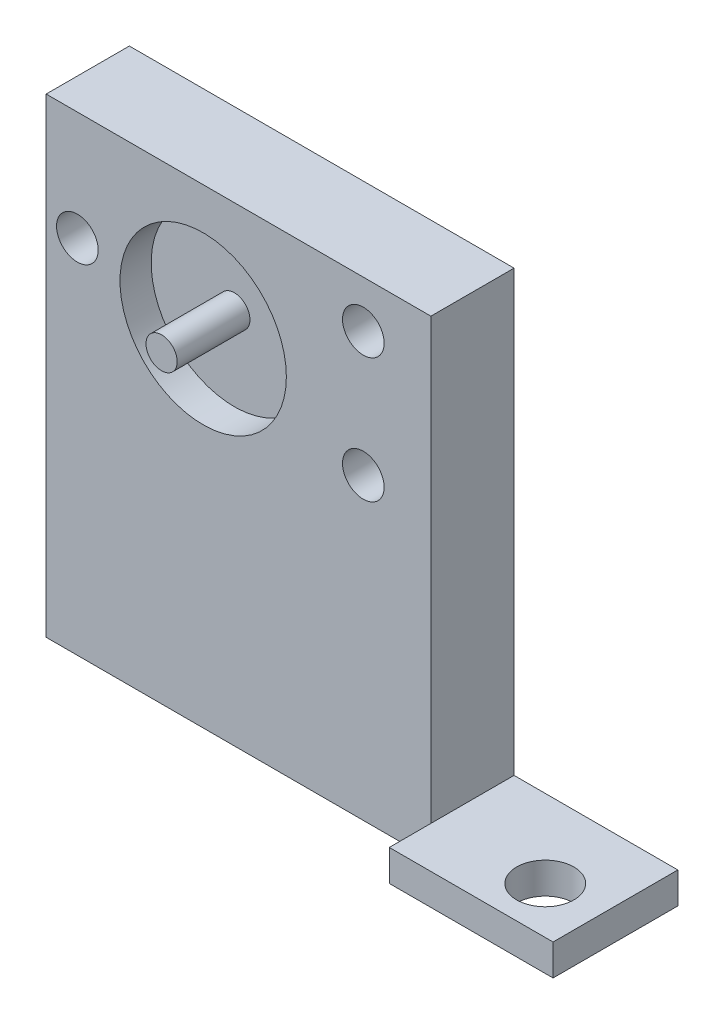
SolidWorks part; units mm, degrees
ref_plane "Plan de face" through (0, 0, 0) normal (0, 0, 1) x (1, 0, 0)
ref_plane "Plan de dessus" through (0, 0, 0) normal (0, 1, 0) x (1, 0, 0)
ref_plane "Plan de droite" through (0, 0, 0) normal (1, 0, 0) x (0, 0, -1)
sketch "Esquisse1" plane through (0, 0, 0) normal (0, 0, 1) x (1, 0, 0)
  line L0 (-2.5, 15.125) -> (9.3, -8.875) construction
  line L1 (18.5, -21.125) -> (-18.5, -21.125)
  line L2 (18.5, -21.125) -> (18.5, 21.125)
  line L3 (18.5, 21.125) -> (-18.5, 21.125)
  line L4 (-18.5, -21.125) -> (-18.5, 21.125)
  line L5 (18.5, -21.125) -> (-18.5, 21.125) construction
  line L6 (18.5, 21.125) -> (-18.5, -21.125) construction
  line L7 (-2.5, 15.125) -> (9.3, 15.125) construction
  line L8 (-2.5, 15.125) -> (-2.5, -8.875) construction
  line L9 (-2.5, -8.875) -> (9.3, -8.875) construction
  line L10 (9.3, 15.125) -> (9.3, -8.875) construction
  circle A0 centre (3.4, 9.125) radius 6
  point P0 (0, 0)
  point P19 (3.4, 3.3872)
  point P25 (3.4, 3.125)
  dimension "D6" = 12
  dimension "D1" = 37
  dimension "D2" = 36.25
  dimension "D3" = 11.8
  dimension "D4" = 24
  dimension "D5" = 16
  dimension "D7" = 6
extrude "Boss.-Extru.1" add sketch "Esquisse1" along normal blind 12 contours A0 | L4 L1 L2 L3 A0 region at (-0.2652, -0.7117, 0) region at (3.4, 9.125, 0)
sketch "Esquisse2" plane through (0, 0, 12) normal (0, 0, 1) x (1, 0, 0)
  line L4 (-18.5, -21.125) -> (18.5, -21.125)
  line L5 (-18.5, 21.125) -> (-18.5, -21.125)
  line L6 (18.5, 21.125) -> (-18.5, 21.125)
  line L7 (18.5, -21.125) -> (18.5, 21.125)
  line L8 (-18.5, -21.125) -> (18.5, -21.125) construction
  line L9 (-18.5, 21.125) -> (-18.5, -21.125) construction
  line L10 (18.5, 21.125) -> (-18.5, 21.125) construction
  line L11 (18.5, -21.125) -> (18.5, 21.125) construction
  circle A0 centre (3.4, 9.125) radius 1.5
  circle A1 centre (3.4, 9.125) radius 6
  circle A2 centre (3.4, 9.125) radius 6
  dimension "D3" = 3
  dimension "D1" = 0
  dimension "D2" = 0
extrude "Enlèv. mat.-Extru.1" cut sketch "Esquisse2" against normal offset from surface (3 mm away) 3 up to face at (0, 0, 12)
sketch "Esquisse3" plane through (0, -21.125, 0) normal (0, -1, 0) x (1, 0, 0)
  line L0 (18.5, 0) -> (-18.5, 0) construction
  line L1 (-18.5, 12) -> (-34.25, 12)
  line L2 (-18.5, 12) -> (-18.5, 0)
  line L3 (-18.5, 0) -> (-34.25, 0)
  line L4 (-34.25, 12) -> (-34.25, 0)
  line L9 (-18.5, 0) -> (18.5, 0)
  line L10 (18.5, 0) -> (18.5, 12)
  line L11 (18.5, 12) -> (-18.5, 12)
  line L12 (-18.5, 12) -> (-18.5, 0)
  line L13 (-18.5, 0) -> (18.5, 0)
  line L14 (18.5, 0) -> (18.5, 12)
  line L15 (18.5, 12) -> (-18.5, 12)
  line L16 (-18.5, 12) -> (-18.5, 0)
  circle A0 centre (-29, 7.5) radius 2.75
  line M6 (-18.5, 0) -> (18.5, 0)
  line M7 (18.5, 0) -> (18.5, 12)
  line M8 (18.5, 12) -> (-18.5, 12)
  line M9 (-18.5, 12) -> (-18.5, 0)
  dimension "D2" = 5.5
  dimension "D1" = 10.5
  dimension "D3" = 5.25
  dimension "D5" = 7.5
  dimension "D4" = 0
extrude "Boss.-Extru.2" add sketch "Esquisse3" along normal blind 3 contours M9 M6 M7 M8 | L1 L4 L3 A0 M9 region at (-25.9976, -21.125, 5.7843) region at (0, -21.125, 6)
sketch "Esquisse4" plane through (0, 0, 12) normal (0, 0, 1) x (1, 0, 0)
  line L1 (-18.5, 21.125) -> (18.5, 21.125)
  line L2 (-18.5, 21.125) -> (-18.5, -24.125)
  line L3 (-18.5, -24.125) -> (18.5, -24.125)
  line L4 (18.5, 21.125) -> (18.5, -24.125)
  circle A0 centre (3.4, 9.125) radius 8
  circle A2 centre (3.4, 9.125) radius 1.5 construction
  circle A3 centre (3.4, 9.125) radius 1.5
  circle A4 centre (3.4, 9.125) radius 6 construction
  circle A5 centre (3.4, 9.125) radius 6 construction
  circle M1 centre (3.4, 9.125) radius 6
  line M2 (-18.5, 21.125) -> (-18.5, -21.125)
  line M5 (-34.25, -24.125) -> (18.5, -24.125)
  line M6 (18.5, -24.125) -> (18.5, 21.125)
  line M7 (18.5, 21.125) -> (-18.5, 21.125)
  dimension "D1" = 2
extrude "Enlèv. mat.-Extru.2" cut sketch "Esquisse4" against normal blind 4 contours L2 M2 M5 M6 M7 M1 region at (-0.464, -2.9501, 12)
extrude "Enlèv. mat.-Extru.4" cut sketch "Esquisse4<3>" against normal offset from surface (7 mm away) 3 contours A3 M1 | A0 M1 region at (-4.3737, 9.125, 12) region at (-2.4303, 9.125, 12) up to face at (11.4, 9.125, 8) offset beyond the face yes
sketch "Esquisse4<3>" plane through (0, 0, 12) normal (0, 0, 1) x (1, 0, 0) same geometry as "Esquisse4"
fillet "Congé2" radius 5 1 edges at (-18.5, -22.625, 8)
fillet "Congé3" radius 5 1 edges at (-18.5, -22.625, 12)
sketch "Esquisse5" plane through (0, 0, 8) normal (0, 0, 1) x (1, 0, 0)
  line L0 (-12, 16.625) -> (-12, 4.625) construction
  line L1 (18.5, 21.125) -> (-18.5, 21.125) construction
  line L2 (-18.5, 21.125) -> (-18.5, -21.125) construction
  circle A0 centre (-12, 16.625) radius 2
  circle A1 centre (-12, 4.625) radius 2
  circle A2 centre (15.5, 10.625) radius 2
  point P6 (-12, 10.625)
  dimension "D1" = 4
  dimension "D2" = 4.5
  dimension "D3" = 6.5
  dimension "D4" = 12
  dimension "D5" = 27.5
extrude "Enlèv. mat.-Extru.5" cut sketch "Esquisse5" against normal through all
extrude "Boss.-Extru.3" add sketch "Esquisse2<2>" along normal blind 2 contours A0 region at (3.4, 9.125, 12)
sketch "Esquisse2<2>" plane through (0, 0, 12) normal (0, 0, 1) x (1, 0, 0) same geometry as "Esquisse2"
ref_plane "Plan1" through (18.5, 0, 0) normal (1, 0, 0) x (0, 0, -1)
mirror "Symétrie1" about plane through (18.5, 0, 12) normal (-1, 0, 0) of "Enlèv. mat.-Extru.5", "Enlèv. mat.-Extru.1", "Boss.-Extru.1", "Enlèv. mat.-Extru.4", "Enlèv. mat.-Extru.2", "Boss.-Extru.2"
sketch "Esquisse6" plane through (18.5, 0, 0) normal (1, 0, 0) x (0, 0, -1)
  line L0 (-12, -24.125) -> (0, -24.125) construction
  line L1 (-14, 21.125) -> (0, 21.125)
  line L2 (-14, 21.125) -> (-14, -24.125)
  line L3 (-14, -24.125) -> (0, -24.125)
  line L4 (0, 21.125) -> (0, -24.125)
  line L5 (-8, 21.125) -> (0, 21.125) construction
  line L6 (-14, 10.625) -> (-14, 7.625) construction
  line L7 (0, -21.125) -> (0, 21.125) construction
  point P6 (-16.8548, 24.4741)
extrude "Enlèv. mat.-Extru.6" cut sketch "Esquisse6" against normal through all
